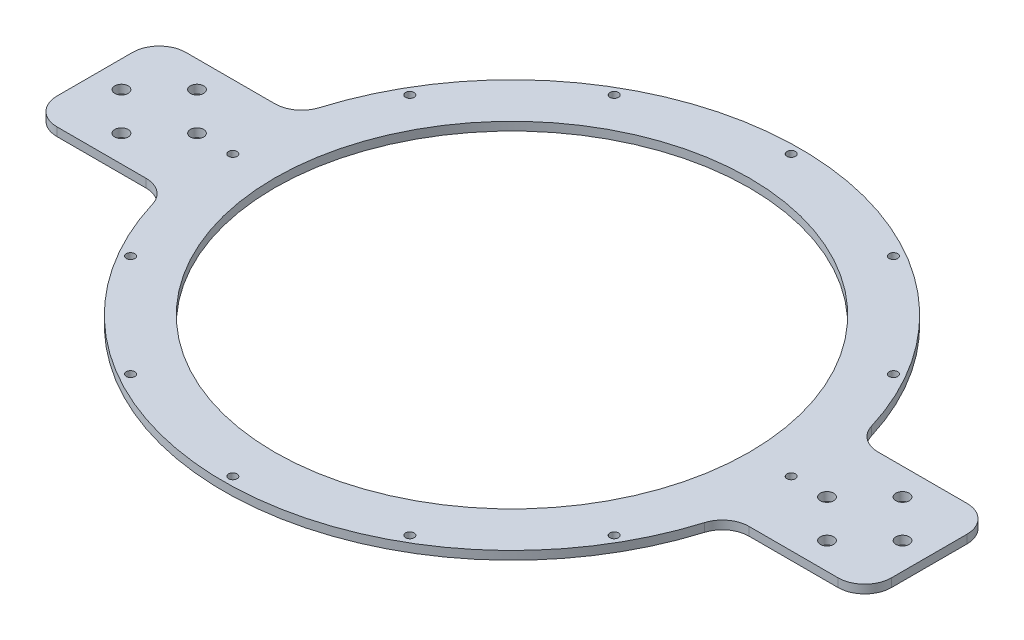
SolidWorks part; units mm, degrees
material "AISI 304"
ref_plane "Front Plane" through (0, 0, 0) normal (0, 0, 1) x (1, 0, 0)
ref_plane "Top Plane" through (0, 0, 0) normal (0, 1, 0) x (1, 0, 0)
ref_plane "Right Plane" through (0, 0, 0) normal (1, 0, 0) x (0, 0, -1)
sketch "Sketch1" plane through (0, 0, 0) normal (0, 1, 0) x (1, 0, 0)
  circle A0 centre (0, 0) radius 88.9
  circle A1 centre (0, 0) radius 107.95
  dimension "D1" = 177.8
  dimension "D2" = 215.9
extrude "Boss-Extrude1" add sketch "Sketch1" along normal blind 3.175
hole_wizard "M3 Clearance Hole1" positions "Sketch9" profile "Sketch10" hole size "M3" standard "ANSI Metric" end condition through all
sketch "Sketch9" plane through (0, 3.175, 0) normal (0, 1, 0) x (1, 0, 0)
  line L0 (0, 0) -> (0, 104.55) construction
  point P2 (0, 104.55)
  dimension "D1" = 104.55
sketch "Sketch10" plane through (0, 3.175, -104.55) normal (1, 0, 0) x (0, 0, 1)
  line L0 (0, 0) -> (0, 3.175)
  line L1 (0, 3.175) -> (1.6, 3.175)
  line L2 (1.6, 3.175) -> (1.6, 0)
  line L5 (1.6, 0) -> (0, 0)
  line L11 (0, -6.35) -> (0, 107.95) construction
  dimension "Thru Hole Dia." = 3.2
  dimension "Thru Hole Depth" = 3.175
pattern_circular "CirPattern1" count 12 over 360 about axis through (0, 3.175, 0) along (0, -1, 0) of "M3 Clearance Hole1"
sketch "Sketch2" plane through (0, 0, 0) normal (0, 1, 0) x (1, 0, 0)
  line L0 (-156.2343, 24.1421) -> (-105.2158, 24.1421)
  line L1 (-105.2158, -24.1421) -> (-156.2343, -24.1421)
  line L2 (-156.2343, -24.1421) -> (-156.2343, 24.1421)
  line L3 (-156.2343, 0) -> (0, 0) construction
  line L4 (-146.2343, 0) -> (-132.0921, 14.1421) construction
  line L5 (-132.0921, 14.1421) -> (-117.95, 0) construction
  line L6 (-117.95, 0) -> (-132.0921, -14.1421) construction
  line L7 (-132.0921, -14.1421) -> (-146.2343, 0) construction
  circle A0 centre (0, 0) radius 107.95 construction
  circle A1 centre (0, 0) radius 107.95 construction
  arc A2 (-105.2158, 24.1421) -> (-105.2158, -24.1421) centre (0, 0) ccw
  point P11 (-107.95, 0)
  dimension "D1" = 20
  dimension "D2" = 10
  dimension "D3" = 10
  dimension "D4" = 10
extrude "Boss-Extrude2" add sketch "Sketch2" along normal up to surface (3.175 mm away) up to face at (-52.275, 3.175, -88.943)
fillet "Fillet1" radius 10 4 edges at (-105.2158, 1.5875, -24.1421) (-156.2343, 1.5875, -24.1421) (-156.2343, 1.5875, 24.1421) (-105.2158, 1.5875, 24.1421)
mirror "Mirror1" about plane through (0, 0, 0) normal (1, 0, 0) of "Boss-Extrude2", "Fillet1"
hole_wizard "#10 Clearance Hole3" positions "Sketch7" profile "Sketch8" hole size "#10" standard "ANSI Inch" end condition through all
sketch "Sketch7" plane through (0, 3.175, 0) normal (0, 1, 0) x (1, 0, 0)
  line L0 (-117.95, 0) -> (-132.0921, -14.1421) construction
  line L1 (-132.0921, -14.1421) -> (-146.2343, 0) construction
  line L2 (-146.2343, 0) -> (-132.0921, 14.1421) construction
  line L3 (-132.0921, 14.1421) -> (-117.95, 0) construction
  line L4 (-117.95, 0) -> (-132.0921, -14.1421) construction
  line L5 (-132.0921, -14.1421) -> (-146.2343, 0) construction
  line L6 (-146.2343, 0) -> (-132.0921, 14.1421) construction
  line L7 (-132.0921, 14.1421) -> (-117.95, 0) construction
  line L8 (0, 107.95) -> (0, -107.95) construction
  line L10 (132.0921, 14.1421) -> (117.95, 0) construction
  line L11 (146.2343, 0) -> (132.0921, 14.1421) construction
  line L12 (132.0921, -14.1421) -> (146.2343, 0) construction
  line L13 (117.95, 0) -> (132.0921, -14.1421) construction
  arc A0 (103.3286, 31.2475) -> (-103.3286, 31.2475) centre (0, 0) ccw construction
  arc A1 (-103.3286, -31.2475) -> (103.3286, -31.2475) centre (0, 0) ccw construction
  point P0 (-132.0921, -14.1421)
  point P2 (-117.95, 0)
  point P4 (-132.0921, 14.1421)
  point P6 (-146.2343, 0)
  point P29 (146.2343, 0)
  point P30 (132.0921, 14.1421)
  point P31 (117.95, 0)
  point P32 (132.0921, -14.1421)
sketch "Sketch8" plane through (-132.0921, 3.175, 14.1421) normal (1, 0, 0) x (0, 0, 1)
  line L0 (0, 0) -> (0, 3.175)
  line L1 (0, 3.175) -> (2.4892, 3.175)
  line L2 (2.4892, 3.175) -> (2.4892, 0)
  line L5 (2.4892, 0) -> (0, 0)
  line L11 (0, -6.35) -> (0, 107.95) construction
  dimension "Thru Hole Dia." = 4.9784
  dimension "Thru Hole Depth" = 3.175
